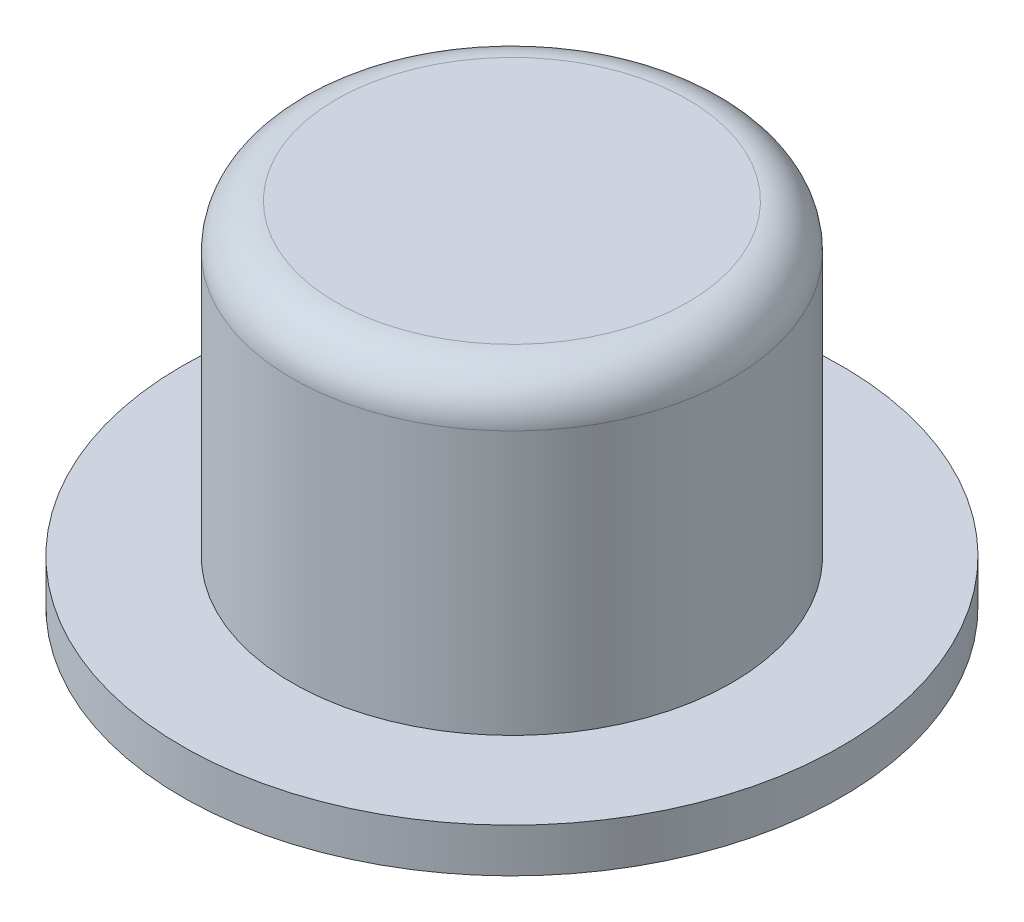
SolidWorks part; units mm, degrees
ref_plane "Front Plane" through (0, 0, 0) normal (0, 0, 1) x (1, 0, 0)
ref_plane "Top Plane" through (0, 0, 0) normal (0, 1, 0) x (1, 0, 0)
ref_plane "Right Plane" through (0, 0, 0) normal (1, 0, 0) x (0, 0, -1)
sketch "Sketch1" plane through (0, 0, 0) normal (0, 0, 1) x (1, 0, 0)
  line L1 (0, 8) -> (5, 8)
  line L2 (5, 8) -> (5, 1)
  line L3 (5, 1) -> (7.5, 1)
  line L4 (7.5, 1) -> (7.5, 0)
  line L6 (0, 8) -> (0, 6.9292) construction
  line L7 (0, 8) -> (0, 0)
  line L10 (0, 0) -> (7.5, 0)
  dimension "D1" = 5
  dimension "D2" = 2.5
  dimension "D3" = 7
  dimension "D4" = 1
revolve "Revolve1" add sketch "Sketch1" angle 360 about L6
sketch "Sketch2" plane through (0, 0, 0) normal (0, -1, 0) x (1, 0, 0)
  line L1 (-1.25, -1.75) -> (1.25, -1.75)
  line L2 (-1.25, -1.75) -> (-1.25, 1.75)
  line L3 (-1.25, 1.75) -> (1.25, 1.75)
  line L4 (1.25, -1.75) -> (1.25, 1.75)
  line L5 (-1.25, -1.75) -> (1.25, 1.75) construction
  line L6 (-1.25, 1.75) -> (1.25, -1.75) construction
  point P0 (0, 0)
  dimension "D1" = 2.5
  dimension "D2" = 3.5
extrude "Cut-Extrude1" cut sketch "Sketch2" against normal blind 3.5 contours L3 L4 L1 L2
fillet "Fillet1" radius 1 1 edges at (-5, 8, 0)
